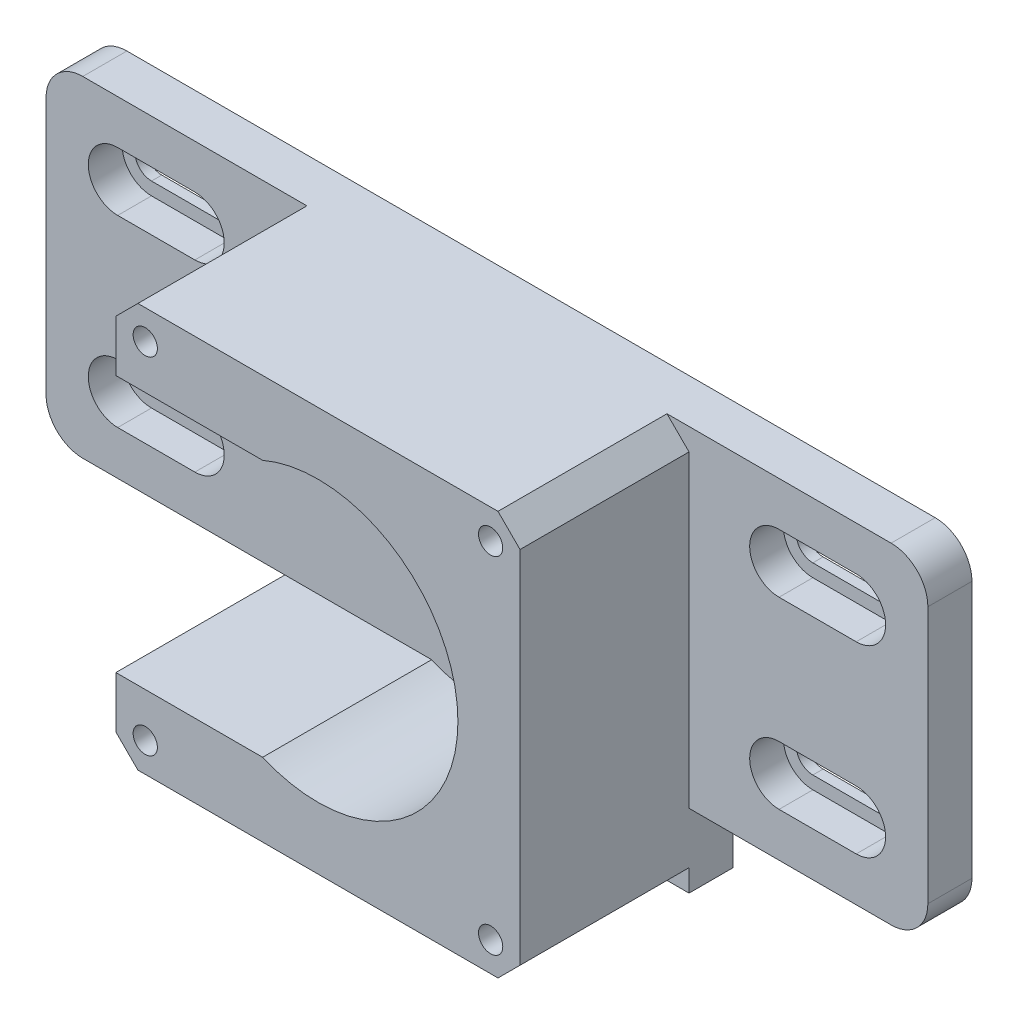
SolidWorks part; units mm, degrees
material "6061 合金"
ref_plane "前视基准面" through (0, 0, 0) normal (0, 0, 1) x (1, 0, 0)
ref_plane "上视基准面" through (0, 0, 0) normal (0, 1, 0) x (1, 0, 0)
ref_plane "右视基准面" through (0, 0, 0) normal (1, 0, 0) x (0, 0, -1)
sketch "草图1" plane through (0, 0, 0) normal (0, 0, 1) x (1, 0, 0)
  line L1 (-27.5, -27.5) -> (27.5, -27.5)
  line L2 (-27.5, -27.5) -> (-27.5, 27.5)
  line L3 (-27.5, 27.5) -> (27.5, 27.5)
  line L4 (27.5, -27.5) -> (27.5, 27.5)
  line L5 (-27.5, -27.5) -> (27.5, 27.5) construction
  line L6 (-27.5, 27.5) -> (27.5, -27.5) construction
  point P0 (0, 0)
  dimension "D1" = 55
  dimension "D2" = 55
extrude "凸台-拉伸1" add sketch "草图1" along normal mid plane 29
sketch "草图2" plane through (0, 0, -14.5) normal (0, 0, -1) x (-1, 0, 0)
  circle A0 centre (0, 0) radius 19.05
  dimension "D1" = 38.1
extrude "切除-拉伸1" cut sketch "草图2" against normal through all
sketch "草图3" plane through (-27.5, 0, 0) normal (1, 0, 0) x (0, 0, -1)
  line L1 (-20, -17.5) -> (20, -17.5)
  line L2 (-20, -17.5) -> (-20, 17.5)
  line L3 (-20, 17.5) -> (20, 17.5)
  line L4 (20, -17.5) -> (20, 17.5)
  line L5 (-20, -17.5) -> (20, 17.5) construction
  line L6 (-20, 17.5) -> (20, -17.5) construction
  point P0 (0, 0)
  dimension "D1" = 40
  dimension "D2" = 35
extrude "切除-拉伸2" cut sketch "草图3" along normal blind 32
chamfer "倒角1" distance 3 angle 45 4 edges at (-27.5, -27.5, 0) (-27.5, 27.5, 0) (27.5, -27.5, 0) (27.5, 27.5, 0)
hole_wizard "M4 螺纹孔1" positions "草图6" profile "草图5" tap size "M4" standard "GB"
sketch "草图6" plane through (0, 0, -14.5) normal (0, 0, -1) x (-1, 0, 0)
  line L0 (0, 19.05) -> (0, -38.2354) construction
  line L2 (-19.05, 0) -> (52.0653, 0) construction
  circle A0 centre (0, 0) radius 19.05 construction
  point P0 (-23.5, 23.5)
  point P3 (23.5, 23.5)
  point P6 (23.5, -23.5)
  point P9 (-23.5, -23.5)
  dimension "D1" = 47
  dimension "D2" = 47
cosmetic thread "孔螺蚊线1" parameters "D1"=12, "D2"=4
cosmetic thread "孔螺蚊线2" parameters "D1"=12, "D2"=4
cosmetic thread "孔螺蚊线3" parameters "D1"=12, "D2"=4
cosmetic thread "孔螺蚊线4" parameters "D1"=12, "D2"=4
sketch "草图5" plane through (23.5, 23.5, -14.5) normal (1, 0, 0) x (0, 1, 0)
  line L0 (0, 0) -> (0, 19.4914)
  line L1 (0, 19.4914) -> (1.65, 18.5)
  line L2 (1.65, 18.5) -> (1.65, 0)
  line L5 (1.65, 0) -> (0, 0)
  line L10 (0, 19.4914) -> (-1.65, 18.5) construction
  line L11 (0, -6.35) -> (0, 107.95) construction
  dimension "螺纹孔钻头直径" = 3.3
  dimension "螺纹孔钻头深度" = 18.5
  dimension "导头角度" = 118
fillet "圆角1" [suppressed] radius 5
hole_wizard "M4 螺纹孔2" positions "草图12" profile "草图11" tap size "M4" standard "GB"
sketch "草图12" plane through (0, 0, 14.5) normal (0, 0, 1) x (1, 0, 0)
  point P0 (23.5, 23.5)
  point P2 (-23.5, 23.5)
  point P4 (-23.5, -23.5)
  point P6 (23.5, -23.5)
sketch "草图11" plane through (23.5, 23.5, 14.5) normal (1, 0, 0) x (0, -1, 0)
  line L0 (0, 0) -> (0, 19.4914)
  line L1 (0, 19.4914) -> (1.65, 18.5)
  line L2 (1.65, 18.5) -> (1.65, 0)
  line L5 (1.65, 0) -> (0, 0)
  line L10 (0, 19.4914) -> (-1.65, 18.5) construction
  line L11 (0, -6.35) -> (0, 107.95) construction
  dimension "螺纹孔钻头直径" = 3.3
  dimension "螺纹孔钻头深度" = 18.5
  dimension "导头角度" = 118
cosmetic thread "孔螺蚊线9" parameters "D1"=12, "D2"=4
cosmetic thread "孔螺蚊线10" parameters "D1"=12, "D2"=4
cosmetic thread "孔螺蚊线11" parameters "D1"=12, "D2"=4
cosmetic thread "孔螺蚊线12" parameters "D1"=12, "D2"=4
sketch "草图13" plane through (0, 0, -14.5) normal (0, 0, -1) x (-1, 0, 0)
  line L1 (-60, -27.5) -> (60, -27.5)
  line L2 (-60, -27.5) -> (-60, 27.5)
  line L3 (-60, 27.5) -> (60, 27.5)
  line L4 (60, -27.5) -> (60, 27.5)
  line L5 (-60, -27.5) -> (60, 27.5) construction
  line L6 (-60, 27.5) -> (60, -27.5) construction
  point P0 (0, 0)
  dimension "D1" = 55
  dimension "D2" = 120
extrude "凸台-拉伸2" add sketch "草图13" against normal blind 6 contours L3 L4 L1 L2
sketch "草图14" plane through (0, 0, -8.5) normal (0, 0, 1) x (1, 0, 0)
  line L0 (-27.5, -17.5) -> (-7.5268, -17.5) construction
  line L1 (-60, -27.5) -> (-27.5, -27.5)
  line L2 (-60, -27.5) -> (-60, -17.5)
  line L3 (-60, -17.5) -> (-27.5, -17.5)
  line L4 (-27.5, -27.5) -> (-27.5, -17.5)
  line L5 (-27.5, -17.5) -> (-27.5, -24.5) construction
  line L6 (27.5, -24.5) -> (27.5, 24.5) construction
  line L7 (27.5, -17.5) -> (60, -17.5)
  line L8 (27.5, -17.5) -> (27.5, -27.5)
  line L9 (27.5, -27.5) -> (60, -27.5)
  line L10 (60, -17.5) -> (60, -27.5)
extrude "切除-拉伸3" cut sketch "草图14" against normal blind 10
hole_wizard "打孔尺寸(%根据)内六角圆柱头螺钉的类型1" positions "草图16" profile "草图15" size "M4" standard "GB" slot yes end condition through all
sketch "草图16" plane through (0, 0, -8.5) normal (0, 0, 1) x (1, 0, 0)
  line L0 (-52.5, 17.5) -> (-37.5, 17.5) construction
  line L1 (60, 27.5) -> (24.5, 27.5) construction
  point P0 (-45, 17.5)
  point P4 (-45, -7.5)
  point P6 (45, 17.5)
  point P8 (45, -7.5)
  dimension "D1" = 15
  dimension "D2" = 90
  dimension "D3" = 45
  dimension "D4" = 10
  dimension "D5" = 25
sketch "草图15" plane through (-45, 17.5, -8.5) normal (1, 0, 0) x (0, -1, 0)
  line L0 (0, 0) -> (0, 6)
  line L1 (0, 6) -> (2.25, 6)
  line L3 (2.25, 6) -> (2.25, 4.6)
  line L4 (2.25, 4.6) -> (4, 4.6)
  line L5 (4, 4.6) -> (4, 0)
  line L7 (4, 0) -> (0, 0)
  line L11 (0, -6.35) -> (0, 107.95) construction
  dimension "通孔孔直径" = 4.5
  dimension "通孔孔深度" = 6
  dimension "柱形沉头孔直径" = 8
  dimension "柱形沉头孔深度" = 4.6
fillet "圆角2" radius 5 4 edges at (60, 27.5, -11.5) (60, -17.5, -11.5) (-60, -17.5, -11.5) (-60, 27.5, -11.5)
